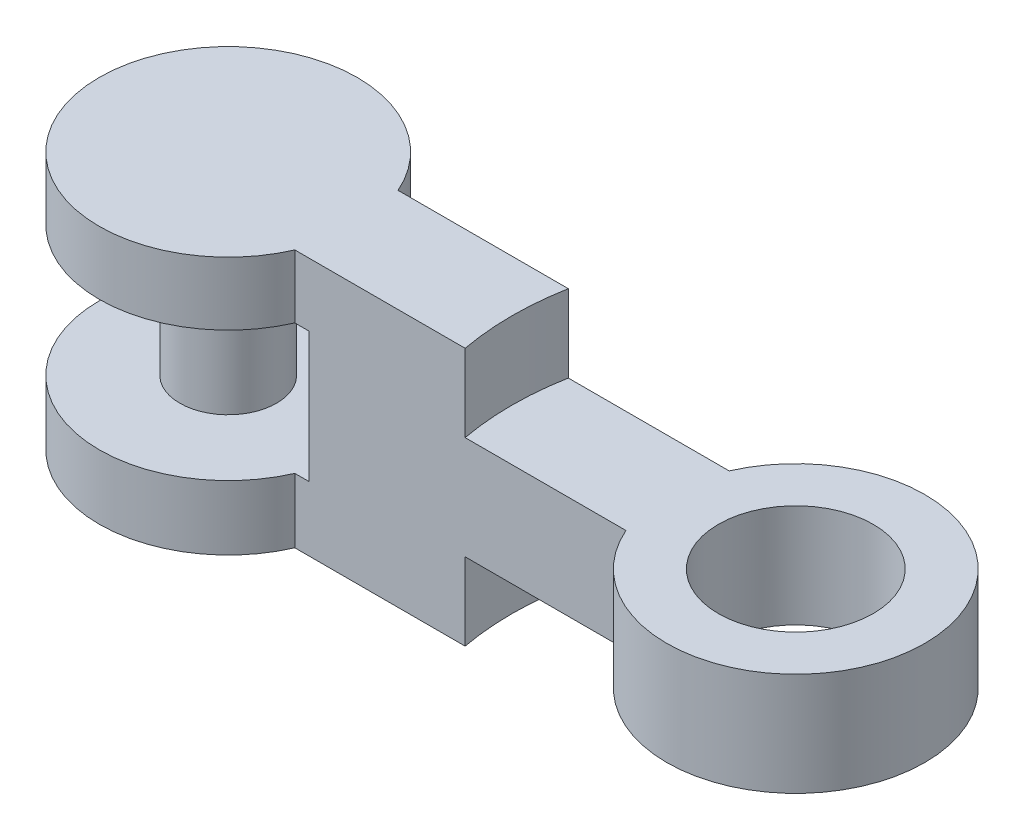
SolidWorks part; units mm, degrees
ref_plane "Front Plane" through (0, 0, 0) normal (0, 0, 1) x (1, 0, 0)
ref_plane "Top Plane" through (0, 0, 0) normal (0, 1, 0) x (1, 0, 0)
ref_plane "Right Plane" through (0, 0, 0) normal (1, 0, 0) x (0, 0, -1)
sketch "Sketch1" plane through (0, 0, 0) normal (0, 1, 0) x (1, 0, 0)
  line L0 (-11, 0) -> (11, 0) construction
  point P4 (0, 0)
  dimension "D1" = 22
sketch "Sketch2" plane through (0, 0, 0) normal (0, 1, 0) x (1, 0, 0)
  line L0 (-11, 2) -> (-11, 0) construction
  line L1 (-11, 0) -> (11, 0) construction
  line L2 (-11, 0) -> (11, 0) construction
  line L3 (-6.4174, -2) -> (6.4174, -2)
  line L4 (-11, 2) -> (11, 2)
  line L5 (-6.4174, 2) -> (6.4174, 2)
  line L6 (-11, -2) -> (-11, 0) construction
  line L8 (-11, -2) -> (-6.4174, -2) construction
  circle A0 centre (-11, 0) radius 5
  circle A1 centre (11, 0) radius 5
  circle A2 centre (-11, 0) radius 1.875
  circle A3 centre (11, 0) radius 3
  dimension "D1" = 10
  dimension "D2" = 3.75
  dimension "5" = 6
  dimension "D4" = 2
  dimension "D3" = 2
extrude "Boss-Extrude1" add sketch "Sketch2" along normal mid plane 10 contours A0 A2 | A1 A3 | A1 L5 A0 L3 region at (0, 0, 0) region at (-15.8586, 0, 0) region at (6.1414, 0, 0)
sketch "Sketch3" plane through (0, 0, 0) normal (0, 1, 0) x (1, 0, 0)
  arc A0 (6.4174, -2) -> (6.4174, 2) centre (11, 0) ccw construction
  arc A1 (-6.4174, 2) -> (-6.4174, -2) centre (-11, 0) ccw construction
  circle A2 centre (11, 0) radius 5 construction
  circle A3 centre (-11, 0) radius 5 construction
  circle A4 centre (-11, 0) radius 5.5
  circle A5 centre (11, 0) radius 5.5
  circle A6 centre (11, 0) radius 11
  dimension "D1" = 0.5
extrude "Cut-Extrude1" cut sketch "Sketch3" along normal through all from offset 2 contours A6
mirror "Mirror2" about plane through (0, 0, 0) normal (0, 1, 0) of "Cut-Extrude1"
sketch "Sketch4" plane through (0, 0, 0) normal (0, 1, 0) x (1, 0, 0)
  circle A0 centre (-11, 0) radius 5 construction
  circle A1 centre (-11, 0) radius 5.5 construction
  circle A2 centre (-11, 0) radius 5 construction
  circle A3 centre (-11, 0) radius 5.5
extrude "Cut-Extrude2" cut sketch "Sketch3<3>" along normal blind 2.55 and the other way blind 2.5 contours A4 region at (-11, 0, 0)
sketch "Sketch3<3>" plane through (0, 0, 0) normal (0, 1, 0) x (1, 0, 0) same geometry as "Sketch3"
sketch "Sketch5" plane through (0, 5, 0) normal (0, 1, 0) x (1, 0, 0)
  circle A0 centre (-11, 0) radius 1.875 construction
  circle A1 centre (-11, 0) radius 1.875
extrude "Boss-Extrude2" add sketch "Sketch5" against normal up to surface (10 mm away) up to face at (-11, -5, 1.875)
equation "\"outer_circle\"= \"totallength\" * 0.2"
equation "\"totallength\"= 50"
equation "\"D1@Sketch2\"=\"outer_circle\""
equation "\"D3@Sketch2\"=\"totallength\" * 0.04"
equation "\"D2@Sketch2\"=\"totallength\" * 0.075"
equation "\"D1@Boss-Extrude1\"=\"outer_circle\""
equation "\"D19@Cut-Extrude1\"=\"totallength\" * 0.04"
equation "\"D1@Cut-Extrude2\"=\"totallength\" * 0.08"
